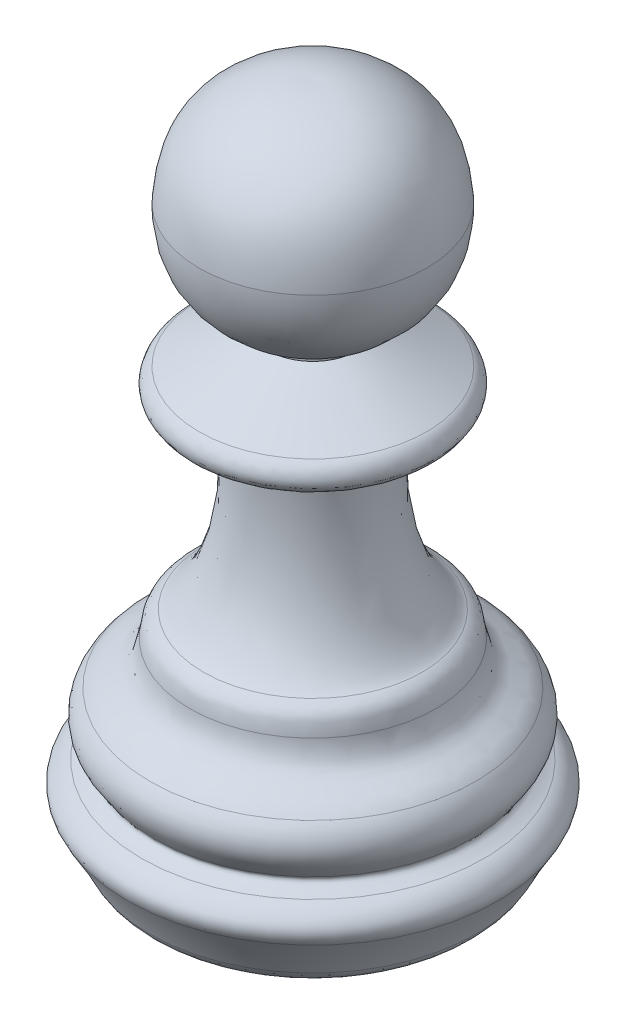
SolidWorks part; units mm, degrees
ref_plane "Front Plane" through (0, 0, 0) normal (0, 0, 1) x (1, 0, 0)
ref_plane "Top Plane" through (0, 0, 0) normal (0, 1, 0) x (1, 0, 0)
ref_plane "Right Plane" through (0, 0, 0) normal (1, 0, 0) x (0, 0, -1)
sketch "Sketch1" plane through (0, 0, 0) normal (0, 0, 1) x (1, 0, 0)
  line L0 (0, 26.6251) -> (0, 0)
  line L1 (-6.2477, 3.8979) -> (0, 3.8979) construction
  line L2 (0, 3.8979) -> (6.2477, 3.8979) construction
  line L3 (1.749, 18.5191) -> (1.749, 18.2829)
  line L4 (1.749, 18.2829) -> (4.479, 16.8884)
  line L5 (4.1468, 15.6897) -> (2.7359, 15.6897)
  line L6 (0, 0) -> (5.5438, 0)
  spline S0 degree 3 poles (0, 26.6251) (1.262, 26.7204) (3.7808, 25.7024) (4.4106, 23.5673) (4.479, 22.4656) knots 0 0 0 0 0.578604 1 1 1 1
  spline S1 degree 2 poles (4.479, 22.4656) (4.4933, 19.7247) (1.749, 18.5191) knots 0 0 0 1 1 1
  spline S2 degree 3 poles (4.479, 16.8884) (4.6795, 16.786) (5.0672, 16.164) (4.4935, 15.6897) (4.1468, 15.6897) knots 0 0 0 0 0.447467 1 1 1 1
  spline S3 degree 3 poles (2.7359, 15.6897) (2.1364, 11.1363) (3.7161, 8.9024) (4.3019, 8.6049) knots 0 0 0 0 1 1 1 1
  spline S4 degree 3 poles (4.3019, 8.6049) (4.4597, 8.5248) (4.7787, 8.2759) (4.7999, 7.8941) (4.834, 7.6252) knots 0 0 0 0 0.408406 1 1 1 1
  spline S5 degree 3 poles (4.834, 7.6252) (4.8747, 7.3037) (5.109, 6.4492) (6.007, 6.3433) (6.4024, 5.9302) knots 0 0 0 0 0.377645 1 1 1 1
  spline S6 degree 3 poles (6.4024, 5.9302) (6.7842, 5.5313) (6.9517, 4.7282) (6.4263, 4.16) (6.2477, 3.8979) knots 0 0 0 0 0.588502 1 1 1 1
  spline S7 degree 3 poles (6.2477, 3.8979) (6.2187, 3.8553) (6.1839, 3.7178) (6.4451, 3.5733) (6.69, 3.498) (6.7414, 3.4785) knots 0 0 0 0 0.162367 0.584346 1 1 1 1
  spline S8 degree 3 poles (6.7414, 3.4785) (6.9707, 3.391) (7.4012, 3.0391) (7.5394, 2.5201) (7.0853, 2.0556) knots 0 0 0 0 0.372722 1 1 1 1
  spline S9 degree 3 poles (7.0853, 2.0556) (6.8647, 1.83) (6.6096, 1.6534) (6.3198, 1.5258) knots 0 0 0 0 1 1 1 1
  spline S10 degree 2 poles (6.3198, 1.5258) (6.8893, 0.6863) (5.5438, 0) knots 0 0 0 1 1 1
  dimension "D1" = 6.2477
  dimension "D2" = 6.2477
revolve "Revolve2" add sketch "Sketch1" angle 360 about L0
fillet "Fillet2" radius 15 1 edges at (0, 1.5258, 6.3198)
